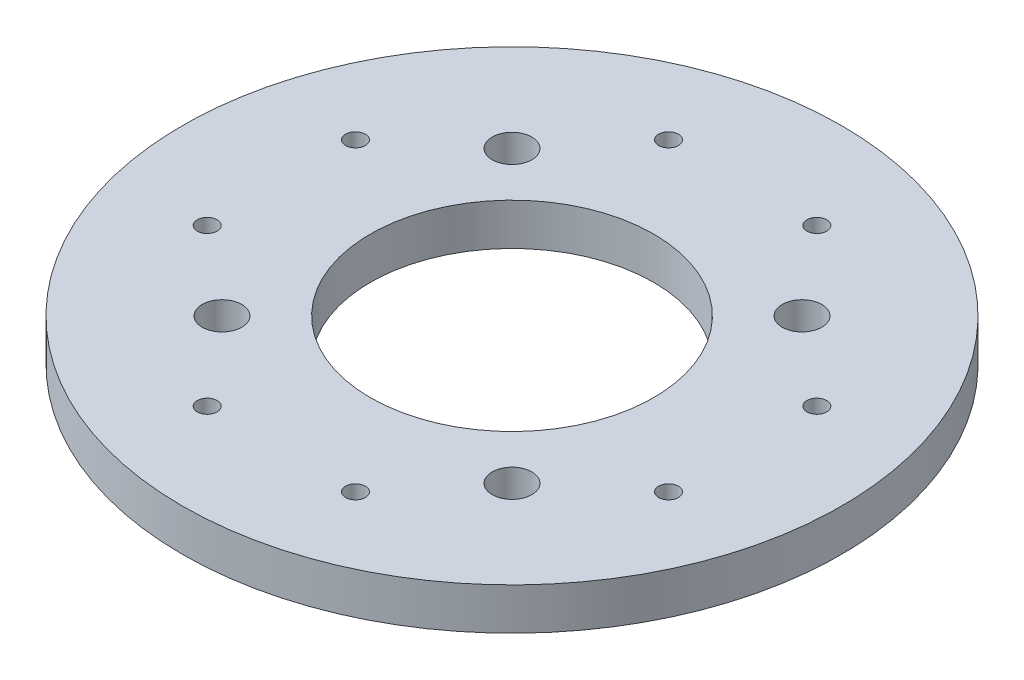
SolidWorks part; units mm, degrees
ref_plane "Front Plane" through (0, 0, 0) normal (0, 0, 1) x (1, 0, 0)
ref_plane "Top Plane" through (0, 0, 0) normal (0, 1, 0) x (1, 0, 0)
ref_plane "Right Plane" through (0, 0, 0) normal (1, 0, 0) x (0, 0, -1)
sketch "Sketch1" plane through (0, 0, 0) normal (0, 1, 0) x (1, 0, 0)
  line L0 (-22, -22) -> (22, 22) construction
  line L1 (-22, -22) -> (-22, 22) construction
  line L3 (-22, -22) -> (22, -22) construction
  line L4 (22, -22) -> (22, 22) construction
  line L5 (-22, 22) -> (22, 22) construction
  line L6 (-22, 22) -> (22, -22) construction
  circle A0 centre (22, 22) radius 3
  circle A1 centre (-22, 22) radius 3
  circle A2 centre (-22, -22) radius 3
  circle A3 centre (22, -22) radius 3
  circle A4 centre (0, 0) radius 50
  circle A5 centre (0, 0) radius 21.5
  dimension "D2" = 6
  dimension "D3" = 100
  dimension "D4" = 43
  dimension "D1" = 44
extrude "Boss-Extrude1" add sketch "Sketch1" along normal blind 6.35
sketch "Sketch2" plane through (0, 6.35, 0) normal (0, 1, 0) x (1, 0, 0)
  circle A0 centre (22, 22) radius 3 construction
  circle A1 centre (22.225, -22.225) radius 5
  circle A2 centre (22.225, -22.225) radius 3
  circle A3 centre (22, 22) radius 3
  circle A4 centre (22, 22) radius 5
  circle A5 centre (-22, -22.45) radius 5
  circle A6 centre (-22, -22.45) radius 3
  circle A7 centre (-22.225, 21.775) radius 5
  circle A8 centre (-22.225, 21.775) radius 3
  point P20 (0, -0.225)
  dimension "D1" = 4
  dimension "D2" = 2
extrude "Boss-Extrude2" [suppressed] add sketch "Sketch2" along normal blind 19.5
ref_plane "Plane1" [suppressed] through (0, 14.75, 0) normal (0, 1, 0) x (1, 0, 0)
mirror "Mirror1" [suppressed] about plane through (0, 14.75, 0) normal (0, 1, 0)
hole_wizard "Ø3.0mm Dowel Hole1" positions "Sketch4" profile "Sketch3" hole size "Ø3.0" standard "ANSI Metric" end condition up to next
sketch "Sketch4" plane through (0, 0, 0) normal (0, -1, 0) x (-1, 0, 0)
  line L0 (0, 0) -> (0, -107.5006) construction
  line L2 (0, 0) -> (-105.3494, 0) construction
  point P0 (-11.25, -35)
  point P15 (11.25, -35)
  point P22 (-35, 11.25)
  point P23 (-35, -11.25)
  point P24 (11.25, 35)
  point P25 (-11.25, 35)
  point P26 (35, -11.25)
  point P27 (35, 11.25)
  point P28 (0, 0)
  dimension "D1" = 11.25
  dimension "D2" = 35
  dimension "D3" = 4
sketch "Sketch3" plane through (11.25, 0, 35) normal (1, 0, 0) x (0, 0, -1)
  line L0 (0, 0) -> (0, 6.35)
  line L1 (0, 6.35) -> (1.5, 6.35)
  line L2 (1.5, 6.35) -> (1.5, 0)
  line L5 (1.5, 0) -> (0, 0)
  line L11 (0, -6.35) -> (0, 107.95) construction
  dimension "Thru Hole Dia." = 3
  dimension "Thru Hole Depth" = 6.35
